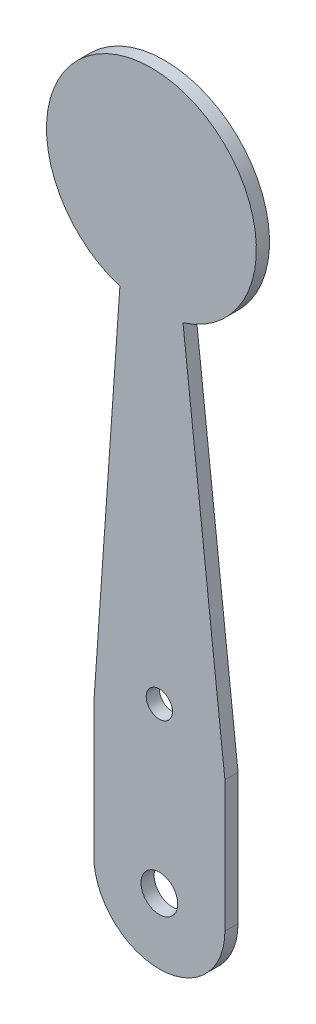
SolidWorks part; units mm, degrees
ref_plane "Alzado" through (0, 0, 0) normal (0, 0, 1) x (1, 0, 0)
ref_plane "Planta" through (0, 0, 0) normal (0, 1, 0) x (1, 0, 0)
ref_plane "Vista lateral" through (0, 0, 0) normal (1, 0, 0) x (0, 0, -1)
sketch "Model" plane through (0, 0, 0) normal (0, 0, 1) x (1, 0, 0)
  line L0 (40.206, -5.7616) -> (42.1979, 22.8197)
  line L1 (50.206, -15.7616) -> (40.206, -15.7616) construction
  line L2 (50.206, -5.7616) -> (50.206, -15.7616)
  line L3 (50.206, -5.7616) -> (47.0109, 22.8197)
  line L8 (40.206, -5.7616) -> (40.206, -15.7616)
  line L15 (45.206, -2.0116) -> (45.206, 22.9884) construction
  line L16 (47.706, 10.4884) -> (55.206, 10.4884) construction
  arc A1 (40.206, -15.7616) -> (50.206, -15.7616) centre (45.206, -15.7616) ccw
  circle A5 centre (45.206, -15.7616) radius 1.4
  circle A6 centre (45.206, -3.2616) radius 1
  arc A15 (42.1979, 22.8197) -> (47.0109, 22.8197) centre (44.6044, 30.4492) cw
  dimension "D2" = 12.5
  dimension "D3" = 10
  dimension "D12" = 10
base flange "Brida base1" sketch "Model" thickness 1 reverse thickness direction no parameters "D1"=0.7366
sketch "Líneas de pliegue1" [suppressed] plane through (0, 0, 0) normal (0, 1, 0) x (1, 0, 0)
sketch "Cuadro delimitador1" [suppressed] plane through (0, 0, 0) normal (0, 1, 0) x (1, 0, 0)
sheet metal parameters "Chapa metálica1" thickness 1 parameters "D1"=0.7366
flat pattern "Chapa desplegada1" [suppressed]
sketch "Líneas de pliegue2" plane through (0, 0, 0) normal (0, 0, 1) x (1, 0, 0)
sketch3d "Cuadro delimitador2" [suppressed]
  line L0 (6.7507, 54.8096, 0) -> (11.3559, -4.1277, 0) construction
  line L1 (-9.2005, 53.5633, 0) -> (-4.5953, -5.3741, 0) construction
  line L2 (6.7507, 54.8096, 0) -> (-9.2005, 53.5633, 0) construction
  line L3 (11.3559, -4.1277, 0) -> (-4.5953, -5.3741, 0) construction
